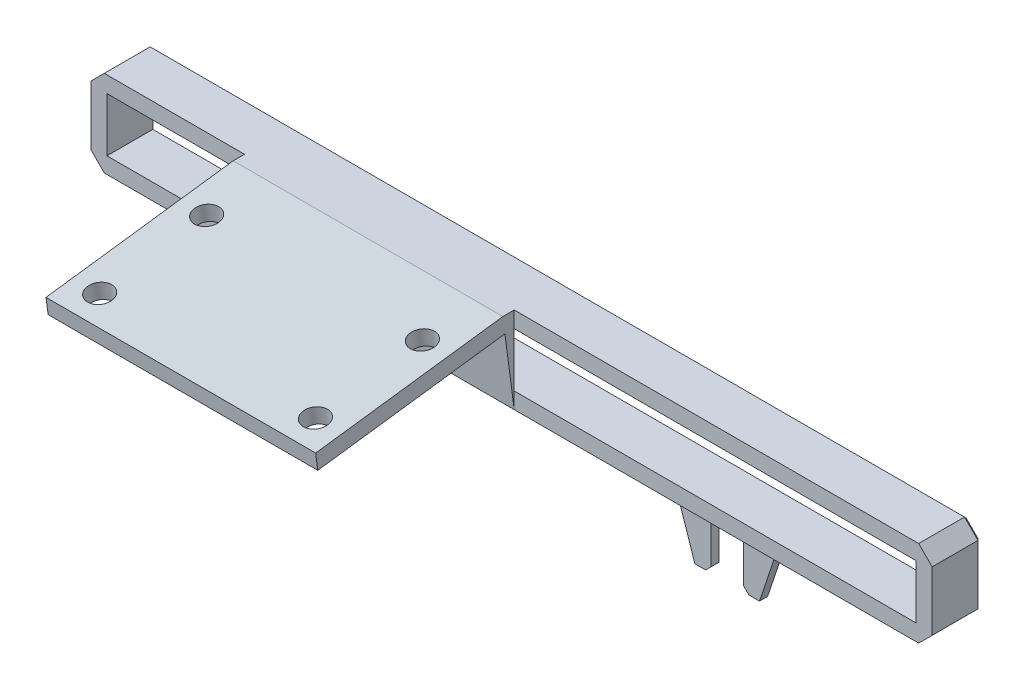
SolidWorks part; units mm, degrees
ref_plane "Top Plane" through (0, 0, 0) normal (0, 0, 1) x (1, 0, 0)
ref_plane "Front Plane" through (0, 0, 0) normal (0, 1, 0) x (1, 0, 0)
ref_plane "Right Plane" through (0, 0, 0) normal (1, 0, 0) x (0, 0, -1)
sketch "Sketch1" plane through (0, 0, 0) normal (0, 0, 1) x (1, 0, 0)
  line L1 (0, 0) -> (156, 0)
  line L2 (0, 0) -> (0, 16)
  line L3 (0, 16) -> (156, 16)
  line L4 (156, 0) -> (156, 16)
  dimension "D1" = 156
  dimension "D2" = 16
extrude "Boss-Extrude1" add sketch "Sketch1" along normal blind 9
sketch "Sketch2" plane through (0, 0, 9) normal (0, 0, 1) x (1, 0, 0)
  line L14 (153, 3) -> (153, 13)
  line L15 (3, 3) -> (153, 3)
  line L16 (3, 13) -> (3, 3)
  line L17 (153, 13) -> (3, 13)
  line L18 (153, 3) -> (153, 13)
  line L19 (3, 3) -> (153, 3)
  line L20 (3, 13) -> (3, 3)
  line L21 (153, 13) -> (3, 13)
  dimension "D1" = 3
extrude "Cut-Extrude1" cut sketch "Sketch2" against normal blind 9
sketch "Sketch4" plane through (156, 0, 0) normal (1, 0, 0) x (0, 0, -1)
  line L0 (-9, 16) -> (-11.1064, 16)
  line L1 (-11.1064, 16) -> (-9, 0)
  line L2 (-9, 0) -> (-9, 16)
  dimension "D1" = 7.5
extrude "Boss-Extrude2" add sketch "Sketch4" along normal blind 50 from offset 127.5 offset against normal yes
sketch "Sketch5" plane through (0, -1.1647, 8.8467) normal (0, -0.1305, 0.9914) x (1, 0, 0)
  line L0 (78.5, 17.3128) -> (78.5, 1.1747) construction
  line L1 (28.5, 17.3128) -> (78.5, 17.3128)
  line L2 (28.5, 17.3128) -> (28.5, 14.3128)
  line L3 (28.5, 14.3128) -> (78.5, 14.3128)
  line L4 (78.5, 17.3128) -> (78.5, 14.3128)
  line L6 (78.5, 17.3128) -> (28.5, 17.3128) construction
  line L7 (28.5, 17.3128) -> (28.5, 1.1747) construction
  dimension "D1" = 3
extrude "Boss-Extrude3" add sketch "Sketch5" along normal blind 35
sketch "Sketch6" plane through (0, 17.1647, 2.2598) normal (0, 0.9914, 0.1305) x (1, 0, 0)
  line L0 (78.5, -8.923) -> (28.5, -8.923) construction
  line L1 (33.5, -18.923) -> (73.5, -18.923)
  line L2 (33.5, -18.923) -> (33.5, -38.923)
  line L3 (33.5, -38.923) -> (73.5, -38.923)
  line L4 (73.5, -18.923) -> (73.5, -38.923)
  line L5 (28.5, -43.923) -> (28.5, -8.923) construction
  dimension "D1" = 40
  dimension "D2" = 20
  dimension "D3" = 10
  dimension "D4" = 5
hole_wizard "M4 Clearance Hole1" positions "Sketch7" profile "Sketch8" hole size "M4" standard "DIN" end condition through all
sketch "Sketch7" plane through (0, 17.1647, 2.2598) normal (0, 0.9914, 0.1305) x (1, 0, 0)
  point P0 (33.5, -18.923)
  point P3 (73.5, -18.923)
  point P6 (73.5, -38.923)
  point P9 (33.5, -38.923)
sketch "Sketch8" plane through (33.5, 14.6947, 21.0209) normal (1, 0, 0) x (0, -0.1305, 0.9914)
  line L0 (0, 0) -> (0, 17.3128)
  line L1 (0, 17.3128) -> (2.25, 17.3128)
  line L2 (2.25, 17.3128) -> (2.25, 0)
  line L5 (2.25, 0) -> (0, 0)
  line L11 (0, -6.35) -> (0, 107.95) construction
  dimension "Thru Hole Dia." = 4.5
  dimension "Thru Hole Depth" = 17.3128
sketch "Sketch10" plane through (0, 0, 0) normal (0, -1, 0) x (1, 0, 0)
  line L0 (0, 0) -> (156, 0) construction
  line L1 (105, 2) -> (117, 2)
  line L2 (105, 2) -> (105, 0)
  line L3 (105, 0) -> (117, 0)
  line L4 (117, 2) -> (117, 0)
  line L5 (156, 9) -> (156, 0) construction
  dimension "D1" = 2
  dimension "D2" = 12
  dimension "D3" = 39
extrude "Boss-Extrude4" add sketch "Sketch10" along normal blind 15
sketch "Sketch11" plane through (0, 0, 0) normal (0, 0, -1) x (-1, 0, 0)
  line L0 (-105, -15) -> (-117, -15) construction
  line L1 (-114, -15) -> (-108, -15)
  line L2 (-114, -15) -> (-114, -4)
  line L3 (-114, -4) -> (-108, -4)
  line L4 (-108, -15) -> (-108, -4)
  line L5 (0, 0) -> (-105, 0) construction
  line L6 (-105, -15) -> (-105, 0) construction
  dimension "D1" = 6
  dimension "D2" = 4
  dimension "D3" = 3
extrude "Cut-Extrude2" cut sketch "Sketch11" against normal blind 15
chamfer "Chamfer1" distance 5 distance2 15 2 edges at (117, 0, 1) (105, 0, 1) first distance on face at (86.3, 0, 4)
chamfer "Chamfer2" distance 1 angle 45 2 edges at (108, -15, 1) (114, -15, 1)
chamfer "Chamfer3" distance 2.5 angle 45 4 edges at (0, 0, 4.5) (0, 16, 4.5) (156, 16, 4.5) (156, 0, 4.5)
chamfer "Chamfer4" distance 2 angle 45 1 edges at (111, 0, 2)
chamfer "Chamfer5" distance 0.5 angle 45 22 edges at (3, 8, 0) (78, 13, 0) (153, 8, 0) (78, 3, 0) (102.5, -7.5, 0) (106, -15, 0) (107.5, -14.5, 0) (108, -9, 0) (111, -4, 0) (114, -9, 0) (114.5, -14.5, 0) (116, -15, 0) (119.5, -7.5, 0) (137.75, 0, 0) (154.75, 1.25, 0) (156, 8, 0) (154.75, 14.75, 0) (78, 16, 0) (1.25, 14.75, 0) (0, 8, 0) (1.25, 1.25, 0) (51.25, 0, 0)
ref_plane "Plane1" through (53.5, 0, 0) normal (-1, 0, 0) x (0, 0, 1)
